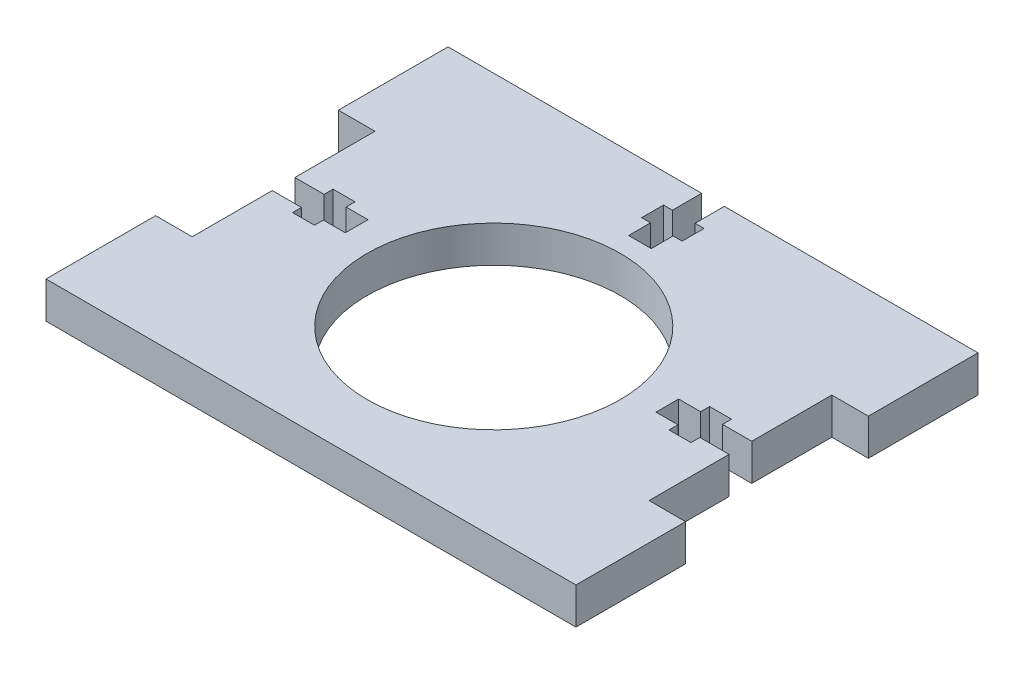
SolidWorks part; units mm, degrees
ref_plane "Plan de face" through (0, 0, 0) normal (0, 0, 1) x (1, 0, 0)
ref_plane "Plan de dessus" through (0, 0, 0) normal (0, 1, 0) x (1, 0, 0)
ref_plane "Plan de droite" through (0, 0, 0) normal (1, 0, 0) x (0, 0, -1)
ref_plane "Plan1" through (0, 5, 0) normal (0, 1, 0) x (1, 0, 0)
sketch "Esquisse1" plane through (0, 5, 0) normal (0, 1, 0) x (1, 0, 0)
  line L0 (31.25, -27.5) -> (31.25, 27.5)
  line L1 (31.25, 27.5) -> (5, 27.5)
  line L2 (5, 27.5) -> (5, -27.5)
  line L3 (5, -27.5) -> (31.25, -27.5)
extrude "Boss.-Extru.1" add sketch "Esquisse1" against normal blind 5
sketch "Esquisse2" plane through (31.25, 0, 0) normal (1, 0, 0) x (0, 0, -1)
  line L0 (27.5, 5) -> (27.5, 0)
  line L1 (27.5, 0) -> (15.45, 0)
  line L2 (15.45, 0) -> (12.5, 2.95)
  line L3 (12.5, 2.95) -> (12.5, 5)
  line L4 (12.5, 5) -> (27.5, 5)
extrude "Boss.-Extru.2" add sketch "Esquisse2" along normal blind 5
sketch "Esquisse3" plane through (31.25, 0, 0) normal (1, 0, 0) x (0, 0, -1)
  line L0 (-15.45, 0) -> (-27.5, 0)
  line L1 (-27.5, 0) -> (-27.5, 5)
  line L2 (-27.5, 5) -> (-12.5, 5)
  line L3 (-12.5, 5) -> (-12.5, 2.95)
  line L4 (-12.5, 2.95) -> (-15.45, 0)
extrude "Boss.-Extru.3" add sketch "Esquisse3" along normal blind 5
sketch "Esquisse4" plane through (0, 0, -27.5) normal (0, 0, -1) x (-1, 0, 0)
  line L0 (-5, 0) -> (-5, 2.95)
  line L1 (-5, 2.95) -> (-7.95, 0)
  line L2 (-7.95, 0) -> (-5, 0)
extrude "Enlèv. mat.-Extru.1" cut sketch "Esquisse4" against normal blind 5
sketch "Esquisse5" plane through (5, 0, 0) normal (-1, 0, 0) x (0, 0, 1)
  line L0 (-22.5, 5) -> (27.5, 5)
  line L1 (27.5, 5) -> (27.5, 0)
  line L2 (27.5, 0) -> (-22.5, 0)
  line L3 (-22.5, 0) -> (-22.5, 5)
extrude "Boss.-Extru.4" add sketch "Esquisse5" along normal blind 36.25
sketch "Esquisse6" plane through (-31.25, 0, 0) normal (-1, 0, 0) x (0, 0, 1)
  line L0 (27.5, 5) -> (27.5, 0)
  line L1 (27.5, 0) -> (15.45, 0)
  line L2 (15.45, 0) -> (12.5, 2.95)
  line L3 (12.5, 2.95) -> (12.5, 5)
  line L4 (12.5, 5) -> (27.5, 5)
extrude "Boss.-Extru.5" add sketch "Esquisse6" along normal blind 5
sketch "Esquisse7" plane through (-31.25, 0, 0) normal (-1, 0, 0) x (0, 0, 1)
  line L0 (-22.5, 5) -> (-12.5, 5)
  line L1 (-12.5, 5) -> (-12.5, 2.95)
  line L2 (-12.5, 2.95) -> (-15.45, 0)
  line L3 (-15.45, 0) -> (-22.5, 0)
  line L4 (-22.5, 0) -> (-22.5, 5)
extrude "Boss.-Extru.6" add sketch "Esquisse7" along normal blind 5
sketch "Esquisse8" plane through (0, 0, -22.5) normal (0, 0, -1) x (-1, 0, 0)
  line L0 (5, 2.95) -> (5, 5)
  line L1 (5, 5) -> (36.25, 5)
  line L2 (36.25, 5) -> (36.25, 0)
  line L3 (36.25, 0) -> (7.95, 0)
  line L4 (7.95, 0) -> (5, 2.95)
extrude "Boss.-Extru.7" add sketch "Esquisse8" along normal blind 5
hole_wizard "Dégagement M301" positions "Esquisse10" profile "Esquisse9" hole size "M30" standard "Ansi Metric"
sketch "Esquisse10" plane through (0, 5, 0) normal (0, 1, 0) x (1, 0, 0)
  point P0 (0, -2.5)
sketch "Esquisse9" plane through (0, 5, 2.5) normal (1, 0, 0) x (0, 0, 1)
  line L0 (0, 0) -> (0, 5)
  line L1 (0, 5) -> (17.325, 5)
  line L2 (17.325, 5) -> (17.325, 0)
  line L5 (17.325, 0) -> (0, 0)
  line L11 (0, -6.35) -> (0, 107.95) construction
  dimension "Diamètre du perçage jusqu'au prochain" = 34.65
  dimension "Profondeur du perçage jusqu'au prochain" = 5
fillet "Congé1" radius 1.6 6 edges at (-33.75, 2.95, 12.5) (-5, 2.95, -25) (-33.75, 2.95, -12.5) (33.75, 2.95, -12.5) (5, 2.95, -25) (33.75, 2.95, 12.5) tangent propagation no
sketch "Esquisse11" plane through (0, 0, 0) normal (0, -1, 0) x (1, 0, 0)
  line L0 (36.25, -27.5) -> (7.95, -27.5) construction
  line L1 (10.0838, -27.5) -> (-9.9495, -27.5)
  line L2 (10.0838, -27.5) -> (10.0838, -21.3098)
  line L3 (10.0838, -21.3098) -> (-9.9495, -21.3098)
  line L4 (-9.9495, -27.5) -> (-9.9495, -21.3098)
  line L6 (-31.25, -15.45) -> (-36.25, -15.45)
  line L7 (-31.25, -15.45) -> (-31.25, -12.5)
  line L8 (-31.25, -12.5) -> (-36.25, -12.5)
  line L9 (-36.25, -15.45) -> (-36.25, -12.5)
  line L10 (-36.25, 12.5) -> (-31.25, 12.5)
  line L11 (-36.25, 12.5) -> (-36.25, 15.45)
  line L12 (-36.25, 15.45) -> (-31.25, 15.45)
  line L13 (-31.25, 12.5) -> (-31.25, 15.45)
  line L14 (31.25, 15.45) -> (36.25, 15.45)
  line L15 (31.25, 15.45) -> (31.25, 12.5)
  line L16 (31.25, 12.5) -> (36.25, 12.5)
  line L17 (36.25, 15.45) -> (36.25, 12.5)
  line L18 (36.25, -12.5) -> (31.25, -12.5)
  line L19 (36.25, -12.5) -> (36.25, -15.45)
  line L20 (36.25, -15.45) -> (31.25, -15.45)
  line L21 (31.25, -12.5) -> (31.25, -15.45)
extrude "Boss.-Extru.8" add sketch "Esquisse11" against normal blind 5
sketch "Esquisse12" plane through (0, 0, 0) normal (0, -1, 0) x (1, 0, 0)
  line L0 (36.25, -27.5) -> (-36.25, -27.5) construction
  line L1 (1.55, -27.5) -> (-1.55, -27.5)
  line L2 (1.55, -27.5) -> (1.55, -17.5)
  line L3 (1.55, -17.5) -> (-1.55, -17.5)
  line L4 (-1.55, -27.5) -> (-1.55, -17.5)
  line L6 (2.78, -23.5) -> (-2.77, -23.5)
  line L7 (2.78, -23.5) -> (2.78, -20.5)
  line L8 (2.78, -20.5) -> (-2.77, -20.5)
  line L9 (-2.77, -23.5) -> (-2.77, -20.5)
  line L18 (31.25, 12.5) -> (31.25, -12.5) construction
  line L19 (31.25, -1.55) -> (21.25, -1.55)
  line L20 (31.25, -1.55) -> (31.25, 1.55)
  line L21 (31.25, 1.55) -> (21.25, 1.55)
  line L22 (21.25, -1.55) -> (21.25, 1.55)
  line L23 (36.25, -12.5) -> (31.25, -12.5) construction
  line L24 (27.25, -2.78) -> (24.25, -2.78)
  line L25 (27.25, -2.78) -> (27.25, 2.77)
  line L26 (27.25, 2.77) -> (24.25, 2.77)
  line L27 (24.25, -2.78) -> (24.25, 2.77)
  line L28 (0, 0) -> (0, 12.6155) construction
  line L29 (-24.25, -2.78) -> (-24.25, 2.77)
  line L30 (-27.25, 2.77) -> (-24.25, 2.77)
  line L31 (-27.25, -2.78) -> (-27.25, 2.77)
  line L32 (-27.25, -2.78) -> (-24.25, -2.78)
  line L33 (-21.25, -1.55) -> (-21.25, 1.55)
  line L34 (-31.25, 1.55) -> (-21.25, 1.55)
  line L35 (-31.25, -1.55) -> (-31.25, 1.55)
  line L36 (-31.25, -1.55) -> (-21.25, -1.55)
  line M7 (31.25, -12.5) -> (31.25, 12.5)
  line M13 (-31.25, 12.5) -> (-31.25, -12.5)
  line M16 (-36.25, -27.5) -> (36.25, -27.5)
  dimension "D1" = 4
  dimension "D2" = 3
  dimension "D3" = 3
  dimension "D4" = 5.55
  dimension "D5" = 3.1
  dimension "D6" = 1.23
  dimension "D7" = 1.55
  dimension "D8" = 10
  dimension "D9" = 3
  dimension "D10" = 3
  dimension "D11" = 5.55
  dimension "D12" = 3.1
  dimension "D13" = 1.23
  dimension "D14" = 10.95
extrude "Enlèv. mat.-Extru.2" cut sketch "Esquisse12" against normal through all contours L2 L6 L4 M16 | L2 L8 L4 L6 | L7 L8 L2 L6 | L8 L2 L3 L4 | L9 L6 L4 L8 | L25 L19 L21 M7 | L27 L19 L25 L21 | L27 L24 L25 L19 | L19 L27 L21 L22 | L27 L21 L25 L26 | L29 L36 L33 L34 | L31 L36 L29 L34 | L36 L31 L32 L29 | L36 L31 L34 M13 | L31 L34 L29 L30 region at (0, 0, -25.5) region at (0, 0, -22) region at (2.165, 0, -22) region at (-2.16, 0, -22) region at (0, 0, -19) region at (29.25, 0, 0) region at (25.75, 0, -2.165) region at (25.75, 0, 0) region at (22.75, 0, 0) region at (25.75, 0, 2.16) region at (-25.75, 0, -2.165) region at (-25.75, 0, 0) region at (-22.75, 0, 0) region at (-25.75, 0, 2.16) region at (-29.25, 0, 0)
